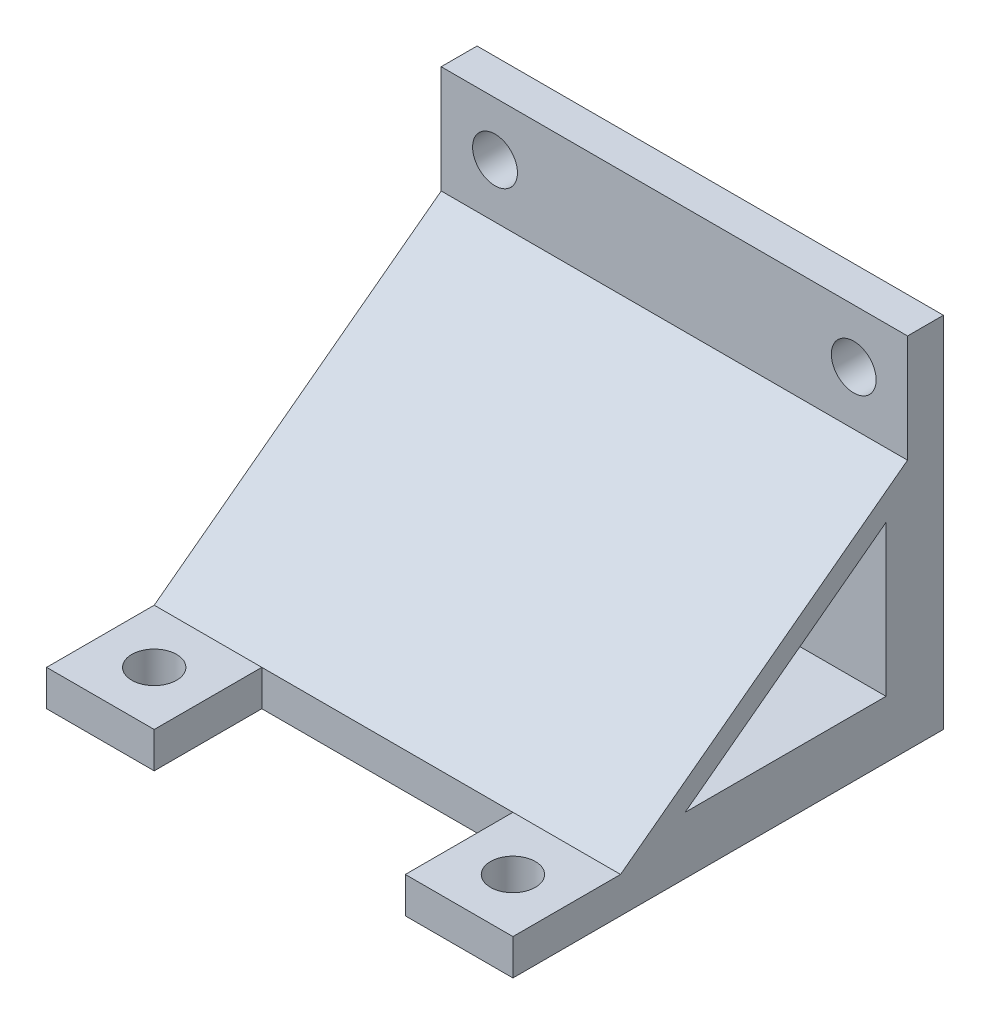
SolidWorks part; units mm, degrees
other "Markup1"
sketch "Sketch16" [suppressed] plane through (60, 62, 45) normal (0.9182, 0.3955, 0.0203) x (-0.0959, 0.2718, -0.9576)
ref_plane "Front" through (0, 0, 0) normal (0, 0, 1) x (1, 0, 0)
ref_plane "Top" through (0, 0, 0) normal (0, 1, 0) x (1, 0, 0)
ref_plane "Right" through (0, 0, 0) normal (1, 0, 0) x (0, 0, -1)
sketch "Sketch1" plane through (0, 0, 0) normal (0, 0, 1) x (1, 0, 0)
  line L1 (-32.5, 0) -> (32.5, 0)
  line L2 (-32.5, 0) -> (-32.5, 50)
  line L3 (-32.5, 50) -> (32.5, 50)
  line L4 (32.5, 0) -> (32.5, 50)
  line L7 (0, 11.4259) -> (0, -9.2664) construction
  point P4 (0, 0)
  dimension "D1" = 50
  dimension "D2" = 65
extrude "Boss-Extrude1" add sketch "Sketch1" along normal blind 10 contours L1 L4 L3 L2 region at (0, 25, 0)
sketch "Sketch2" plane through (0, 0, 0) normal (0, 1, 0) x (1, 0, 0)
  line L0 (0, 7.4706) -> (0, -16.6901) construction
  line L1 (-25, 85) -> (-25, 5) construction
  line L2 (-32.5, 0) -> (-17.5, 0)
  line L3 (-32.5, 0) -> (-32.5, 91)
  line L4 (-32.5, 91) -> (-17.5, 91)
  line L5 (-17.5, 0) -> (-17.5, 91)
  line L8 (17.5, 0) -> (17.5, 91)
  line L9 (32.5, 91) -> (17.5, 91)
  line L10 (32.5, 0) -> (32.5, 91)
  line L11 (32.5, 0) -> (17.5, 0)
  line L12 (-21.75, 85) -> (-21.75, 5)
  line L15 (-28.25, 85) -> (-28.25, 5)
  line L16 (25, 85) -> (25, 5) construction
  line L17 (21.75, 85) -> (21.75, 5)
  line L18 (28.25, 85) -> (28.25, 5)
  arc A4 (-21.75, 85) -> (-28.25, 85) centre (-25, 85) ccw
  arc A5 (-28.25, 5) -> (-21.75, 5) centre (-25, 5) ccw
  arc A6 (21.75, 85) -> (28.25, 85) centre (25, 85) cw
  arc A7 (28.25, 5) -> (21.75, 5) centre (25, 5) cw
  point P9 (-25, 45)
  point P17 (25, 45)
  dimension "D3" = 3.25
  dimension "D5" = 5
  dimension "D1" = 91
  dimension "D2" = 15
  dimension "D4" = 6
extrude "Boss-Extrude3" [suppressed] add sketch "Sketch2" along normal blind 5
sketch "Sketch7" plane through (0, 0, 10) normal (0, 0, 1) x (1, 0, 0)
  line L1 (-32.5, 50) -> (32.5, 50)
  line L2 (-32.5, 50) -> (-32.5, 0)
  line L3 (-32.5, 0) -> (32.5, 0)
  line L4 (32.5, 50) -> (32.5, 0)
extrude "Boss-Extrude5" add sketch "Sketch7" along normal blind 50
sketch "Sketch8" plane through (-32.5, 0, 0) normal (-1, 0, 0) x (0, 0, 1)
  line L0 (60, 50) -> (5, 50)
  line L1 (60, 50) -> (0, 50) construction
  line L2 (5, 50) -> (5, 35)
  line L3 (5, 35) -> (45, 5)
  line L5 (45, 5) -> (60, 5)
  line L6 (60, 50) -> (60, 0) construction
  line L7 (60, 5) -> (60, 50)
  line L8 (0, 0) -> (0, 50) construction
  dimension "D1" = 5
  dimension "D2" = 15
  dimension "D3" = 15
  dimension "D4" = 5
extrude "Cut-Extrude4" cut sketch "Sketch8" against normal through all
sketch "Sketch9" plane through (0, 0, 5) normal (0, 0, 1) x (1, 0, 0)
  line L0 (19, 56.4751) -> (19, -5.9092) construction
  line L1 (32.5, 50) -> (-32.5, 50) construction
  line L2 (0, 50) -> (0, 0) construction
  line L3 (-19, 58.7509) -> (-19, -17.8238) construction
  circle A0 centre (-25, 42.5) radius 3.125
  circle A3 centre (25, 42.5) radius 3.125
  dimension "D1" = 6.25
  dimension "D2" = 25
  dimension "D3" = 7.5
  dimension "D4" = 19
  dimension "D5" = 19
extrude "Cut-Extrude5" cut sketch "Sketch9" against normal through all
sketch "Sketch10" plane through (0, 5, 0) normal (0, 1, 0) x (1, 0, 0)
  line L0 (0, 0) -> (0, -60) construction
  line L1 (32.5, -60) -> (-32.5, -60) construction
  circle A0 centre (-25, -52.5) radius 3.125
  circle A2 centre (25, -52.5) radius 3.125
  dimension "D1" = 6.25
  dimension "D2" = 7.5
  dimension "D3" = 25
extrude "Cut-Extrude6" cut sketch "Sketch10" against normal through all
sketch "Sketch11" [suppressed] plane through (0, 0, 10) normal (0, 0, 1) x (1, 0, 0)
  line L0 (-32.5, 0) -> (32.5, 0) construction
  line L1 (-32.5, 50) -> (-17.5, 50)
  line L2 (-32.5, 50) -> (-32.5, 0)
  line L3 (-32.5, 0) -> (-17.5, 0)
  line L4 (-17.5, 50) -> (-17.5, 0)
  line L6 (0, 50) -> (0, 0) construction
  line L7 (-32.5, 50) -> (32.5, 50) construction
  line L8 (17.5, 50) -> (17.5, 0)
  line L9 (32.5, 0) -> (17.5, 0)
  line L10 (32.5, 50) -> (32.5, 0)
  line L11 (32.5, 50) -> (17.5, 50)
  dimension "D1" = 15
extrude "Boss-Extrude6" [suppressed] add sketch "Sketch11" along normal blind 35
sketch "Sketch12" [suppressed] plane through (-32.5, 0, 0) normal (-1, 0, 0) x (0, 0, 1)
  line L0 (10, 50) -> (10, 35)
  line L1 (45, 50) -> (0, 50) construction
  line L2 (10, 35) -> (35, 5)
  line L3 (35, 5) -> (45, 5)
  line L4 (45, 50) -> (45, 0) construction
  line L5 (45, 5) -> (45, 50)
  line L6 (45, 50) -> (10, 50)
  line L7 (45, 0) -> (-122, 0) construction
  line L8 (0, 5) -> (0, 50) construction
  dimension "D1" = 15
  dimension "D2" = 5
  dimension "D3" = 10
  dimension "D4" = 10
extrude "Cut-Extrude7" [suppressed] cut sketch "Sketch12" against normal through all
sketch "Sketch20" [suppressed] plane through (0, 0, 10) normal (0, 0, 1) x (1, 0, 0)
  line L0 (32.5, 50) -> (32.5, 0) construction
  line L5 (-32.5, 50) -> (32.5, 50)
  line L6 (-32.5, 50) -> (-32.5, 55)
  line L7 (-32.5, 55) -> (32.5, 55)
  line L8 (32.5, 50) -> (32.5, 55)
  dimension "D1" = 5
extrude "Boss-Extrude7" [suppressed] add sketch "Sketch20" against normal up to surface (10 mm away) up to face at (-21.875, 42.5, 0)
sketch "Sketch13" [suppressed] plane through (0, 0, 10) normal (0, 0, 1) x (1, 0, 0)
  line L0 (0, 62) -> (0, 0) construction
  line L1 (32.5, 55) -> (-32.5, 55) construction
  circle A0 centre (-25, 47.5) radius 3.125
  circle A1 centre (25, 47.5) radius 3.125
  dimension "D1" = 6.25
  dimension "D2" = 7.5
  dimension "D3" = 25
extrude "Cut-Extrude8" [suppressed] cut sketch "Sketch13" against normal blind 15
sketch "Sketch14" [suppressed] plane through (0, 5, 0) normal (0, 1, 0) x (1, 0, 0)
  line L1 (-17.5, -45) -> (-32.5, -45) construction
  line L2 (-17.5, -45) -> (-32.5, -45)
  line L3 (-32.5, -35) -> (-32.5, -45) construction
  line L4 (-32.5, -35) -> (-32.5, -45)
  line L5 (0, 0) -> (0, -45) construction
  circle A0 centre (-25, -40) radius 3.125
  circle A1 centre (25, -40) radius 3.125
  point P2 (-25, -45)
  point P6 (-32.5, -40)
  dimension "D1" = 6.25
extrude "Cut-Extrude9" [suppressed] cut sketch "Sketch14" against normal blind 15 contours A0 | A1
sketch "Sketch19" plane through (0, 0, 0) normal (1, 0, 0) x (0, 0, -1)
  line L0 (-5, 35) -> (-45, 5) construction
  line L1 (-5, 35) -> (-45, 5)
  line L2 (-5, 35) -> (-5, 5)
  line L3 (-5, 5) -> (-45, 5)
  line L4 (-8, 29) -> (-8, 8)
  line L5 (-8, 8) -> (-36, 8)
  line L6 (-8, 29) -> (-36, 8)
  dimension "D1" = 3
extrude "Cut-Extrude11" cut sketch "Sketch19" against normal through all both and the other way through all contours L4 L6 L5 | L4 L6 region at (0, 15, 17.3333)
sketch "Sketch21" [suppressed] plane through (0, 0, 0) normal (0, 1, 0) x (1, 0, 0)
  line L0 (0, 10.9853) -> (0, -16.7679) construction
  line L1 (32.5, -10) -> (-32.5, -10) construction
  line L2 (32.5, 0) -> (47.5, 0)
  line L3 (32.5, 0) -> (32.5, -10)
  line L4 (32.5, -10) -> (47.5, -10)
  line L5 (47.5, 0) -> (47.5, -10)
  line L6 (34.1921, -5) -> (44.0025, -5) construction
  line L7 (32.5, 0) -> (47.5, 0)
  line L8 (32.5, -10) -> (47.5, -10)
  line L9 (32.5, 0) -> (47.5, 0)
  line L10 (32.5, -10) -> (47.5, -10)
  line L11 (32.5, 0) -> (47.5, 0)
  line L12 (32.5, -10) -> (47.5, -10)
  line L13 (32.5, 0) -> (47.5, 0)
  line L14 (32.5, -10) -> (47.5, -10)
  line L15 (32.5, 0) -> (47.5, 0)
  line L16 (32.5, -10) -> (47.5, -10)
  line L17 (32.5, 0) -> (47.5, 0)
  line L18 (32.5, -10) -> (47.5, -10)
  line L19 (32.5, 0) -> (47.5, 0)
  line L20 (32.5, -10) -> (47.5, -10)
  line L21 (32.5, 0) -> (47.5, 0)
  line L22 (32.5, -10) -> (47.5, -10)
  line L23 (32.5, 0) -> (47.5, 0)
  line L24 (32.5, -10) -> (47.5, -10)
  line L25 (-32.5, -10) -> (-47.5, -10)
  line L26 (-47.5, 0) -> (-47.5, -10)
  line L27 (-32.5, 0) -> (-47.5, 0)
  line L28 (-32.5, 0) -> (-32.5, -10)
  circle A0 centre (40, -5) radius 3.25
  circle A1 centre (-40, -5) radius 3.25
  dimension "D1" = 6.5
  dimension "D2" = 15
  dimension "D3" = 40
extrude "Boss-Extrude8" [suppressed] add sketch "Sketch21" along normal blind 10 contours L5 L2 L3 L4 A0 | L28 L27 L26 L25 A1
sketch "Sketch22" plane through (0, 0, 0) normal (0, -1, 0) x (1, 0, 0)
  line L5 (0, -9.137) -> (0, 25.65) construction
  line L6 (-32.5, 0) -> (32.5, 0) construction
  line L7 (20, 0) -> (-20, 0)
  line L8 (20, 0) -> (20, 30)
  line L9 (20, 30) -> (-20, 30)
  line L10 (-20, 0) -> (-20, 30)
  line L11 (-32.5, 60) -> (32.5, 60) construction
  line L12 (-17.5, 60) -> (17.5, 60)
  line L13 (-17.5, 60) -> (-17.5, 45)
  line L14 (-17.5, 45) -> (17.5, 45)
  line L15 (17.5, 60) -> (17.5, 45)
  line L16 (-17.5, 60) -> (17.5, 45) construction
  line L17 (-17.5, 45) -> (17.5, 60) construction
  circle A1 centre (25, 52.5) radius 3.125 construction
  point P11 (0, 52.5)
  dimension "D1" = 5
  dimension "D2" = 30
  dimension "D3" = 7.5
  dimension "D4" = 15
extrude "Cut-Extrude12" cut sketch "Sketch22" against normal up to surface (8 mm away) and the other way through all up to face at (0, 8, 22)
sketch "Sketch23" [suppressed] plane through (0, 0, 0) normal (0, 0, 1) x (1, 0, 0)
  circle A0 centre (0, 25) radius 12.5
  dimension "D1" = 25
  dimension "D2" = 25
extrude "Cut-Extrude13" [suppressed] cut sketch "Sketch23" against normal through all both and the other way through all
